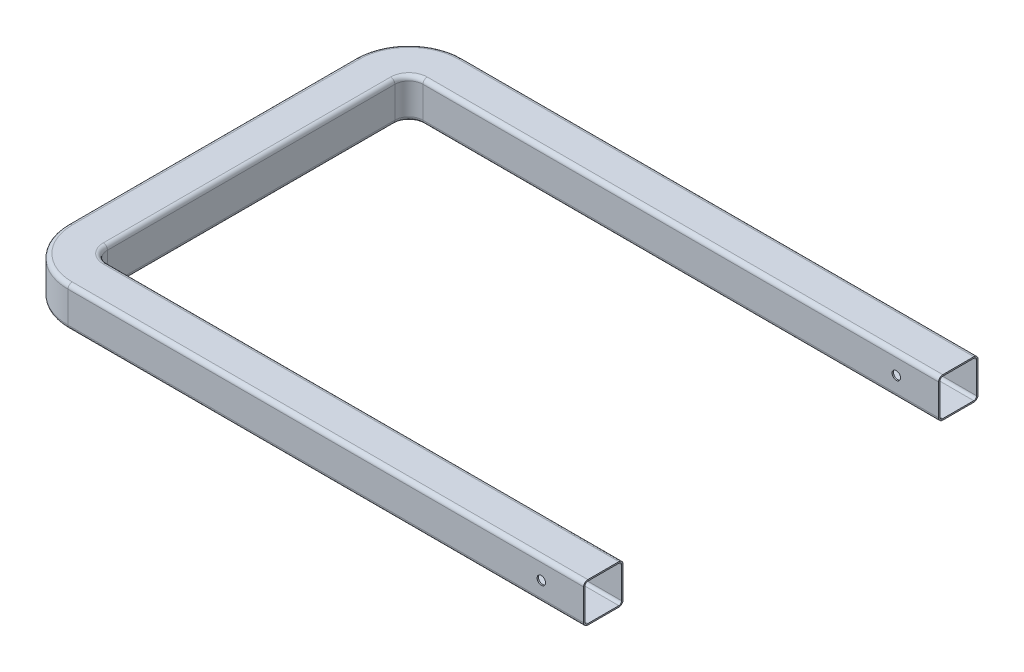
SolidWorks part; units mm, degrees
material "5052-H38, Rod (SS)"
ref_plane "Front Plane" through (0, 0, 0) normal (0, 0, 1) x (1, 0, 0)
ref_plane "Top Plane" through (0, 0, 0) normal (0, 1, 0) x (1, 0, 0)
ref_plane "Right Plane" through (0, 0, 0) normal (1, 0, 0) x (0, 0, -1)
sketch "Sketch1" plane through (0, 0, 0) normal (0, 1, 0) x (1, 0, 0)
  line L0 (0, 0) -> (-610, 0)
  line L1 (-650, 40) -> (-650, 380)
  line L2 (-610, 420) -> (0, 420)
  line L3 (-50, 0) -> (-50, 420) construction
  line L4 (-650, 210) -> (-657.5631, 210) construction
  arc A0 (-610, 0) -> (-650, 40) centre (-610, 40) cw
  arc A1 (-610, 420) -> (-650, 380) centre (-610, 380) ccw
  point P7 (-650, 0)
  point P10 (-650, 420)
  dimension "D3" = 40
  dimension "D1" = 650
  dimension "D2" = 420
  dimension "D4" = 50
sketch "Sketch2" plane through (0, 0, 0) normal (1, 0, 0) x (0, 0, -1)
  line L1 (-18.35, -23.35) -> (18.35, -23.35)
  line L2 (-23.35, -18.35) -> (-23.35, 18.35)
  line L3 (-18.35, 23.35) -> (18.35, 23.35)
  line L4 (23.35, -18.35) -> (23.35, 18.35)
  line L5 (-23.35, -23.35) -> (23.35, 23.35) construction
  line L6 (-23.35, 23.35) -> (23.35, -23.35) construction
  arc A0 (-18.35, 23.35) -> (-23.35, 18.35) centre (-18.35, 18.35) ccw
  arc A1 (-23.35, -18.35) -> (-18.35, -23.35) centre (-18.35, -18.35) ccw
  arc A2 (18.35, -23.35) -> (23.35, -18.35) centre (18.35, -18.35) ccw
  arc A3 (23.35, 18.35) -> (18.35, 23.35) centre (18.35, 18.35) ccw
  point P0 (0, 0)
  dimension "D3" = 5
  dimension "D1" = 46.7
  dimension "D2" = 46.7
sweep "Sweep-Thin1" add profiles "Sketch2" path "Sketch1" parameters "D1"=1.65
sketch "Sketch3" plane through (0, 0, 0) normal (0, 0, 1) x (1, 0, 0)
  line L0 (0, 0) -> (-610, 0) construction
  circle A0 centre (-50, 0) radius 5
  dimension "D1" = 50
extrude "Cut-Extrude1" cut sketch "Sketch3" against normal through all and the other way through all
sketch "Sketch4" plane through (0, 0, -21.7) normal (0, 0, 1) x (1, 0, 0)
  line L0 (0, 0) -> (45, 0) construction
  line L1 (0, -18.35) -> (0, 18.35) construction
  circle A0 centre (-50, 0) radius 5 construction
ref_plane "Plane1" through (-650, 0, 0) normal (1, 0, 0) x (0, 0, -1)
sketch "Sketch5" plane through (-650, 0, 0) normal (1, 0, 0) x (0, 0, -1)
  line L0 (380, 0) -> (38.7593, 0) construction
  line L1 (209.3797, 0) -> (281.8797, 0) construction
  line L3 (209.3797, 0) -> (136.8797, 0) construction
  line L4 (281.8797, 0) -> (281.8797, -50) construction
  line L5 (136.8797, 0) -> (136.8797, -50) construction
  dimension "D1" = 72.5
  dimension "D2" = 72.5
ref_plane "Plane2" through (0, 0, -210) normal (0, 0, -1) x (-1, 0, 0)
